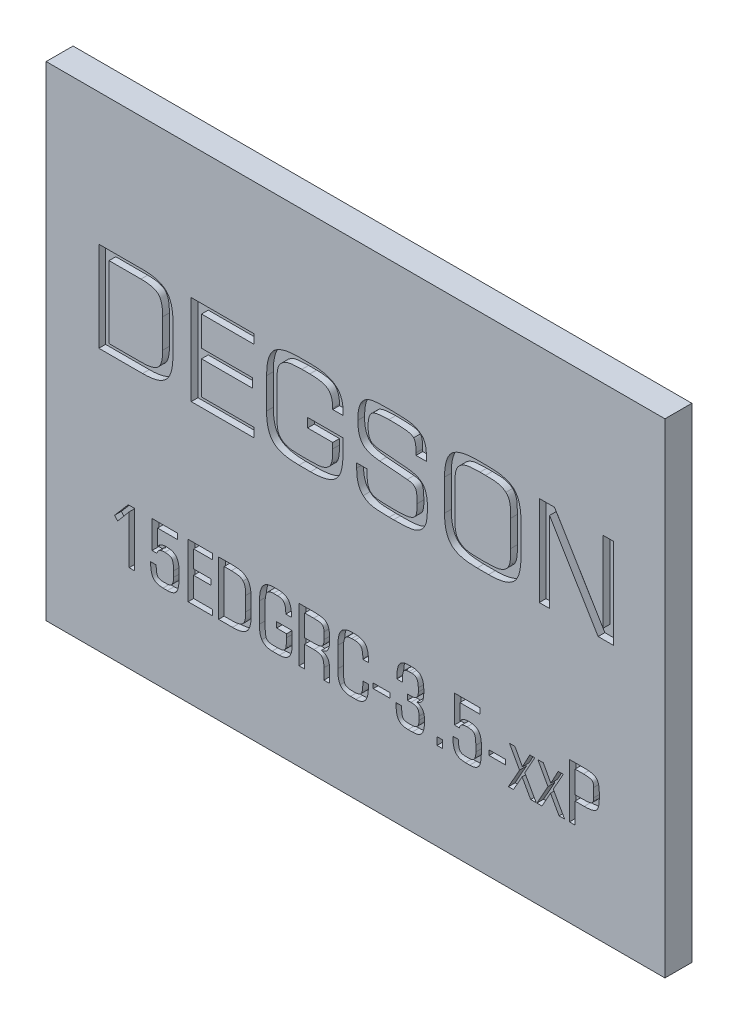
SolidWorks part; units mm, degrees
ref_plane "Спереди" through (0, 0, 0) normal (0, 0, 1) x (1, 0, 0)
ref_plane "Сверху" through (0, 0, 0) normal (0, 1, 0) x (1, 0, 0)
ref_plane "Справа" through (0, 0, 0) normal (1, 0, 0) x (0, 0, -1)
sketch "Эскиз1" plane through (0, 0, 0) normal (0, 0, 1) x (1, 0, 0)
  line L8 (-4.6, -3.6) -> (4.6, -3.6)
  line L9 (4.6, -3.6) -> (4.6, 3.6)
  line L10 (4.6, 3.6) -> (-4.6, 3.6)
  line L11 (-4.6, 3.6) -> (-4.6, -3.6)
extrude "Бобышка-Вытянуть1" add sketch "Эскиз1" along normal blind 0.4 contours L10 L11 L8 L9
sketch "Эскиз2" plane through (0, 0, 0.4) normal (0, 0, 1) x (1, 0, 0)
  line L0 (-4.6, 0.3) -> (4.6, 0.3) construction
  line L1 (-4.6, 3.6) -> (-4.6, -3.6) construction
  line L2 (4.6, -3.6) -> (4.6, 3.6) construction
  line L4 (-4.6, 0) -> (-4.6, 3.6) construction
  line L5 (-4.6, 1.8) -> (4.6, 1.8) construction
  line L6 (-4.6, 0) -> (-4.6, -3.6) construction
  line L7 (-4.6, -1.8) -> (4.6, -1.8) construction
  line L8 (-4.6, -2.3) -> (4.6, -2.3) construction
  text T0 "DEGSON" font "Square721 BT" height in points 5
  text T1 "15EDGRC-3.5-xxP" font "Square721 Cn BT" height in points 3
  dimension "D1" = 1.5
  dimension "D2" = 0.5
extrude "Вырез-Вытянуть1" cut sketch "Эскиз2" against normal blind 0.1
sketch "Эскиз3" plane through (0, 0, 0) normal (0, 0, -1) x (-1, 0, 0)
  line L0 (-4.6, 3.6) -> (-4.6, 0) construction
  line L1 (-4.6, -3.6) -> (-4.6, 3.6) construction
  line L2 (-4.6, 0) -> (-4.6, -3.6) construction
  line L3 (-4.6, -1.8) -> (4.6, -1.8) construction
  line L4 (4.6, 3.6) -> (4.6, -3.6) construction
  line L5 (-4.6, 1.8) -> (4.6, 1.8) construction
  line L6 (-4.6, 0.3) -> (4.6, 0.3) construction
  line L7 (-4.6, -2.3) -> (4.6, -2.3) construction
  text T0 "DEGSON" font "Square721 BT" height in points 5
  text T1 "15EDGRC-3.5-xxP" font "Square721 Cn BT" height in points 3
  dimension "D1" = 1.5
  dimension "D2" = 0.5
extrude "Вырез-Вытянуть2" cut sketch "Эскиз3" against normal blind 0.1
